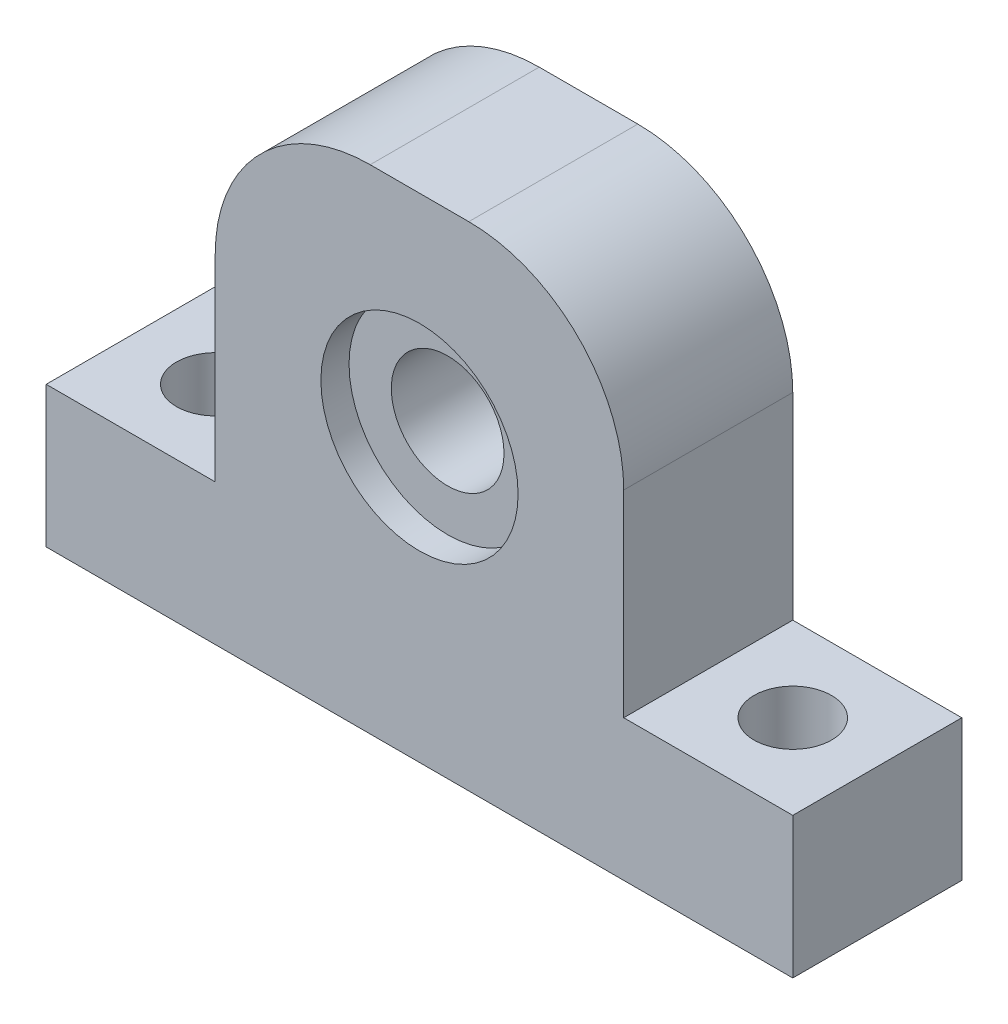
SolidWorks part; units mm, degrees
ref_plane "前视基准面" through (0, 0, 0) normal (0, 0, 1) x (1, 0, 0)
ref_plane "上视基准面" through (0, 0, 0) normal (0, 1, 0) x (1, 0, 0)
ref_plane "右视基准面" through (0, 0, 0) normal (1, 0, 0) x (0, 0, -1)
sketch "草图1" plane through (0, 0, 0) normal (0, 0, 1) x (1, 0, 0)
  line L0 (0, 12.796) -> (0, -15.4359) construction
  line L1 (3.5, 15) -> (-3.5, 15)
  line L2 (-14.5, 4) -> (-14.5, -10)
  line L3 (-14.5, -10) -> (-26.5, -10)
  line L4 (-26.5, -10) -> (-26.5, -20)
  line L5 (-26.5, -20) -> (26.5, -20)
  line L6 (26.5, -10) -> (26.5, -20)
  line L7 (14.5, -10) -> (26.5, -10)
  line L8 (14.5, 4) -> (14.5, -10)
  circle A0 centre (0, 0) radius 4
  arc A1 (-3.5, 15) -> (-14.5, 4) centre (-3.5, 4) ccw
  arc A2 (3.5, 15) -> (14.5, 4) centre (3.5, 4) cw
  point P17 (0, -20)
  point P19 (0, 15)
  dimension "D1" = 8
  dimension "D2" = 26.5
  dimension "D5" = 11
  dimension "D3" = 10
  dimension "D4" = 14.5
  dimension "D6" = 35
  dimension "D7" = 20
extrude "凸台-拉伸1" add sketch "草图1" along normal blind 6 and the other way blind 6
sketch "草图2" plane through (0, 0, 6) normal (0, 0, 1) x (1, 0, 0)
  circle A0 centre (0, 0) radius 7
  dimension "D1" = 14
extrude "切除-拉伸1" cut sketch "草图2" against normal blind 2
sketch "草图3" plane through (0, 0, -6) normal (0, 0, -1) x (-1, 0, 0)
  circle A0 centre (0, 0) radius 7
  dimension "D1" = 14
extrude "切除-拉伸2" cut sketch "草图3" against normal blind 2
sketch "草图4" plane through (0, -20, 0) normal (0, -1, 0) x (1, 0, 0)
  line L0 (0, 14.3005) -> (0, -12.32) construction
  circle A0 centre (-20.5, 0) radius 2.75
  circle A1 centre (20.5, 0) radius 2.75
  dimension "D1" = 20.5
  dimension "D2" = 5.5
extrude "切除-拉伸3" cut sketch "草图4" against normal blind 17
